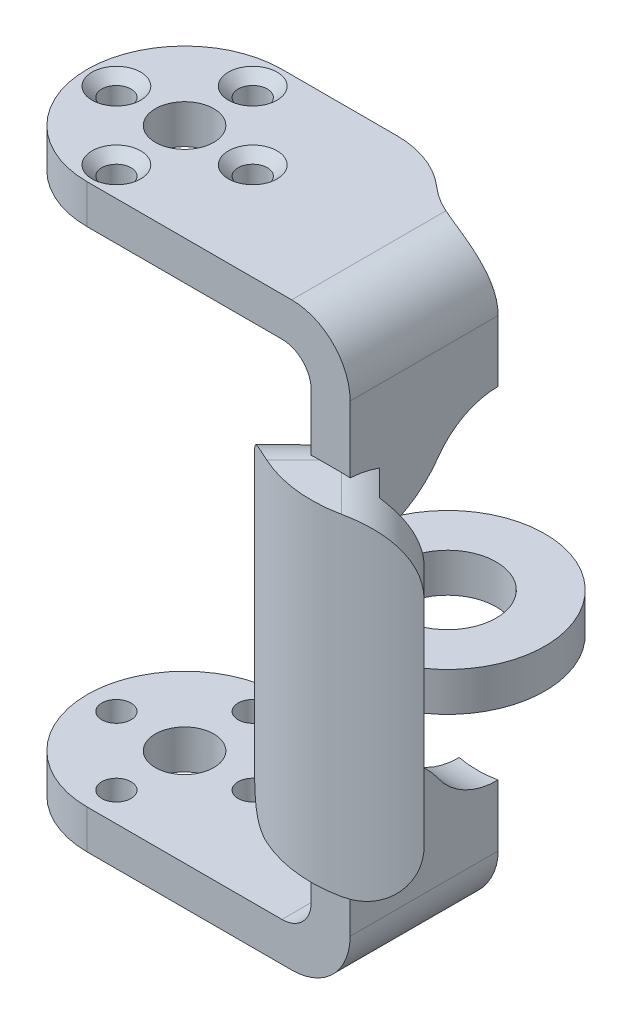
SolidWorks part; units mm, degrees
ref_plane "Спереди" through (0, 0, 0) normal (0, 0, 1) x (1, 0, 0)
ref_plane "Сверху" through (0, 0, 0) normal (0, 1, 0) x (1, 0, 0)
ref_plane "Справа" through (0, 0, 0) normal (1, 0, 0) x (0, 0, -1)
sketch "Sketch1" plane through (0, 0, 0) normal (0, 1, 0) x (1, 0, 0)
  line L1 (0, -10) -> (27, -10)
  line L2 (0, -10) -> (0, 10)
  line L3 (0, 10) -> (27, 10)
  line L4 (27, -10) -> (27, 10)
  circle A0 centre (0, 0) radius 10
  dimension "D1" = 20
  dimension "D2" = 20
  dimension "D3" = 27
extrude "Boss-Extrude1" add sketch "Sketch1" along normal blind 59.6 contours L2 A0 | L2 A0 | A0 L1 L4 L3 region at (17.2969, 0, 0) region at (-4.2441, 0, 0) region at (4.2441, 0, 0)
sketch "Sketch2" plane through (0, 0, 10) normal (0, 0, 1) x (1, 0, 0)
  line L0 (-10, 59.6) -> (-10, 0) construction
  line L1 (-10, 4) -> (23, 4)
  line L2 (-10, 4) -> (-10, 55.6)
  line L3 (-10, 55.6) -> (23, 55.6)
  line L4 (23, 4) -> (23, 55.6)
  line L5 (-10, 0) -> (0, 0) construction
  line L6 (0, 59.6) -> (-10, 59.6) construction
  line L7 (27, 59.6) -> (27, 0) construction
  dimension "D1" = 4
  dimension "D2" = 4
  dimension "D3" = 4
extrude "Cut-Extrude1" cut sketch "Sketch2" against normal blind 59.6
sketch "Sketch3" plane through (0, 59.6, 0) normal (0, 1, 0) x (1, 0, 0)
  circle A0 centre (0, 0) radius 7 construction
  circle A1 centre (-7, 0) radius 1.5
  circle A2 centre (0, 7) radius 1.5
  circle A3 centre (7, 0) radius 1.5
  circle A4 centre (0, -7) radius 1.5
  point P14 (0, 0)
  dimension "D1" = 14
  dimension "D2" = 3
  dimension "D3" = 4
extrude "Cut-Extrude2" cut sketch "Sketch3" against normal through all
chamfer "Chamfer1" distance 1 angle 45 8 edges at (-7, 0, 1.5) (0, 0, 8.5) (7, 0, 1.5) (0, 0, -5.5) (0, 59.6, -5.5) (7, 59.6, 1.5) (0, 59.6, 8.5) (-7, 59.6, 1.5)
sketch "Sketch4" plane through (0, 59.6, 0) normal (0, 1, 0) x (1, 0, 0)
  circle A0 centre (0, 0) radius 3
  dimension "D1" = 6
extrude "Cut-Extrude3" cut sketch "Sketch4" against normal through all
sketch "Sketch6" plane through (27, 0, 0) normal (1, 0, 0) x (0, 0, -1)
  line L0 (10, 59.6) -> (10, 0) construction
  line L1 (30, 19.8) -> (-10, 19.8)
  line L2 (30, 19.8) -> (30, 39.8)
  line L3 (30, 39.8) -> (-10, 39.8)
  line L4 (-10, 19.8) -> (-10, 39.8)
  line L5 (30, 19.8) -> (-10, 39.8) construction
  line L6 (30, 39.8) -> (-10, 19.8) construction
  line L7 (-10, 59.6) -> (-10, 0) construction
  point P0 (10, 29.8)
  dimension "D1" = 20
extrude "Cut-Extrude4" cut sketch "Sketch6" against normal blind 59.6
ref_plane "Plane1" through (0, 29.8, 0) normal (0, -1, 0) x (-1, 0, 0)
sketch "Sketch5" plane through (0, 29.8, 0) normal (0, -1, 0) x (-1, 0, 0)
  line L1 (-27, -10) -> (-27, 10) construction
  circle A1 centre (-27, 0) radius 10
  dimension "D1" = 20
extrude "Boss-Extrude2" add sketch "Sketch5" along normal mid plane 4 separate body
sketch "Sketch8" plane through (0, 29.8, 0) normal (0, -1, 0) x (-1, 0, 0)
  line L0 (-27, -10) -> (-27, 10) construction
  line L1 (-19.1676, -6.2172) -> (-16.3202, -9.0522)
  line L3 (-32.7728, -8.1655) -> (-35.6236, -11.0288)
  arc A0 (-32.7728, -8.1655) -> (-19.1676, -6.2172) centre (-27, 0) ccw
  arc A1 (-35.6236, -11.0288) -> (-16.3202, -9.0522) centre (-27, 0) ccw
  dimension "D1" = 28
extrude "Boss-Extrude3" add sketch "Sketch8" along normal mid plane 34
sketch "Sketch11" plane through (0, 27.8, 0) normal (0, -1, 0) x (1, 0, 0)
  circle A0 centre (27, 0) radius 5
  dimension "D1" = 10
extrude "Cut-Extrude5" cut sketch "Sketch11" against normal blind 4
fillet "Fillet1" radius 3 2 edges at (23, 55.6, 0) (23, 4, 0)
fillet "Fillet2" radius 6 6 edges at (17.7439, 12.8, 7.6347) (17.7439, 46.8, 7.6347) (34.1982, 46.8, 9.5971) (34.1982, 12.8, 9.5971) (27, 59.6, 0) (27, 0, 0)
chamfer "Chamfer3" distance 3 angle 45 4 edges at (27, 43.2842, 10) (27, 16.3158, 10) (23, 43.2387, 9.1652) (23, 16.3613, 9.1652) first distance on face at (27, 46.7137, 2) first distance on face at (25.5618, 19.5795, 8.6905) first distance on face at (23, 46.3755, 3.0548)
sketch "Sketch12" plane through (0, 0, 0) normal (0, -1, 0) x (1, 0, 0)
  line L0 (0, -10) -> (21, -10) construction
  circle A0 centre (25, -15) radius 10
  dimension "D1" = 20
  dimension "D2" = 25
  dimension "D3" = 5
extrude "Cut-Extrude6" cut sketch "Sketch12" against normal blind 20
mirror "Mirror1" about plane through (0, 29.8, 0) normal (0, -1, 0) of "Cut-Extrude6"
sketch "Sketch14" plane through (27, 0, 0) normal (1, 0, 0) x (0, 0, -1)
  circle A0 centre (5.202, 19.8) radius 7.5
  dimension "D1" = 15
extrude "Cut-Extrude7" cut sketch "Sketch14" against normal blind 15
mirror "Mirror2" about plane through (0, 29.8, 0) normal (0, -1, 0) of "Cut-Extrude7"
fillet "Fillet3" radius 10 4 edges at (16.3397, 57.6, -10) (25, 39.8, 2.298) (25, 19.8, 2.298) (16.3397, 2, -10)
